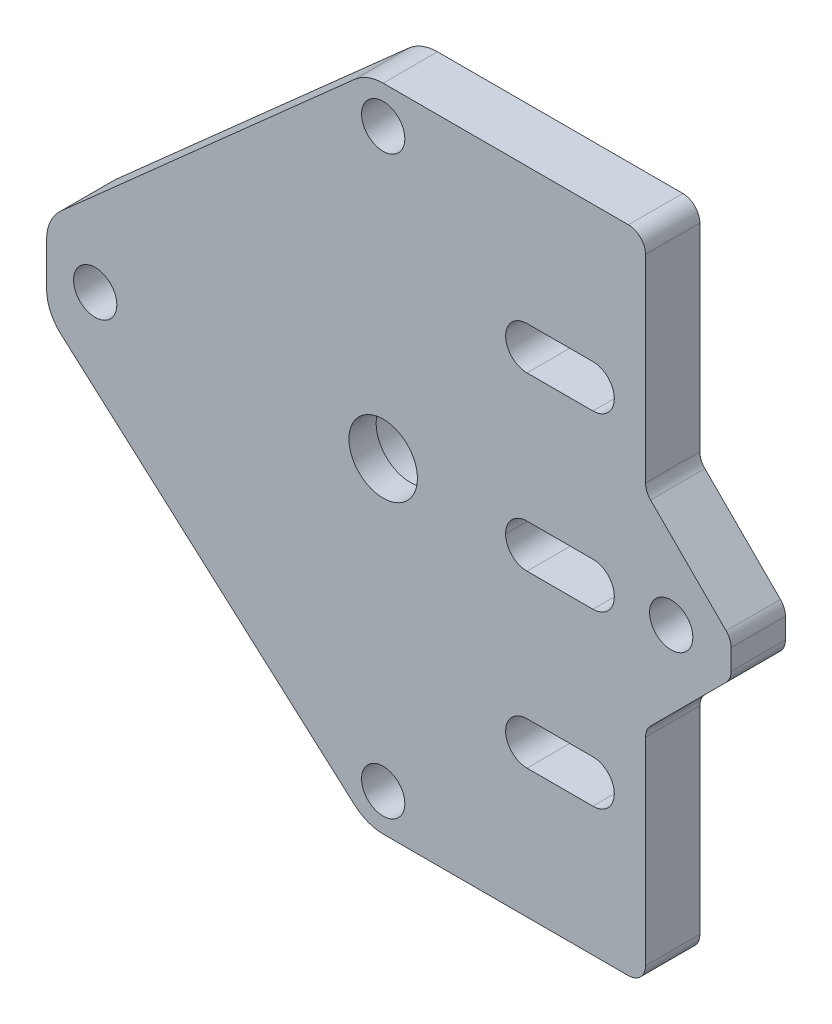
SolidWorks part; units mm, degrees
ref_plane "Front Plane" through (0, 0, 0) normal (0, 0, 1) x (1, 0, 0)
ref_plane "Top Plane" through (0, 0, 0) normal (0, 1, 0) x (1, 0, 0)
ref_plane "Right Plane" through (0, 0, 0) normal (1, 0, 0) x (0, 0, -1)
sketch "Sketch1" plane through (0, 0, 0) normal (0, 0, 1) x (1, 0, 0)
  line L0 (12.9983, -19.5801) -> (-20.66, -19.5801) construction
  line L1 (8, -57.5801) -> (-20.66, -57.5801)
  line L2 (10, -55.5801) -> (10, -32.435)
  line L3 (8, 18.4199) -> (-20.66, 18.4199)
  line L4 (-60, -17.0801) -> (-60, -22.0801)
  line L5 (-20.66, -53.2384) -> (-20.66, 14.0504) construction
  line L6 (-23.9803, 17.1582) -> (-58.3203, -13.3418)
  line L8 (-23.9803, -56.3185) -> (-58.3203, -25.8185)
  line L9 (10, 16.4199) -> (10, -6.7253)
  line L10 (-20.66, 14.0504) -> (-20.66, 18.4199) construction
  line L12 (-20.66, -53.2384) -> (-20.66, -57.5801) construction
  line L14 (-20.66, -19.5801) -> (-54.3183, -19.5801) construction
  line L16 (-54.3183, -19.5801) -> (-60, -19.5801) construction
  line L23 (10.5859, -31.0206) -> (19.4141, -22.1943)
  line L24 (20, -20.7799) -> (20, -18.3803)
  line L25 (19.4141, -16.966) -> (10.5859, -8.1396)
  line L28 (12.9983, -19.5801) -> (20, -19.5801) construction
  circle A0 centre (-20.66, -19.5801) radius 4
  circle A1 centre (-54.3183, -19.5801) radius 2.5277
  circle A2 centre (-20.66, 14.0504) radius 2.5277
  circle A3 centre (12.9983, -19.5801) radius 2.5277
  circle A4 centre (-20.66, -53.2384) radius 2.5277
  arc A5 (10.5859, -8.1396) -> (10, -6.7253) centre (12, -6.7253) cw
  arc A6 (20, -18.3803) -> (19.4141, -16.966) centre (18, -18.3803) ccw
  arc A7 (19.4141, -22.1943) -> (20, -20.7799) centre (18, -20.7799) ccw
  arc A8 (10, -32.435) -> (10.5859, -31.0206) centre (12, -32.435) cw
  arc A9 (-60, -22.0801) -> (-58.3203, -25.8185) centre (-55, -22.0801) ccw
  arc A10 (-23.9803, 17.1582) -> (-20.66, 18.4199) centre (-20.66, 13.4199) cw
  arc A11 (-60, -17.0801) -> (-58.3203, -13.3418) centre (-55, -17.0801) cw
  arc A12 (-23.9803, -56.3185) -> (-20.66, -57.5801) centre (-20.66, -52.5801) ccw
  arc A13 (10, 16.4199) -> (8, 18.4199) centre (8, 16.4199) ccw
  arc A14 (10, -55.5801) -> (8, -57.5801) centre (8, -55.5801) cw
  point P24 (-49.574, 10.4211)
  point P58 (10, -7.5538)
  point P65 (-49.574, -49.5814)
  point P67 (-26.66, 18.5627)
  point P74 (-26.66, -56.4373)
  dimension "D3" = 8
  dimension "D6" = 2
  dimension "D7" = 76
  dimension "D10" = 33.6583
  dimension "D11" = 5.0555
  dimension "D13" = 2
  dimension "D14" = 5
  dimension "D15" = 5
  dimension "D12" = 4.3417
  dimension "D2" = 10
  dimension "D4" = 30.66
  dimension "D5" = 70
  dimension "D8" = 5
  dimension "D9" = 67.2888
  dimension "D16" = 23.1451
extrude "Boss-Extrude1" add sketch "Sketch1" along normal blind 6.35
hole_wizard "Ø5.0mm Dowel Slot1" positions "Sketch3" profile "Sketch2" size "Ø5.0" standard "ANSI Metric" slot yes
sketch "Sketch3" plane through (0, 0, 6.35) normal (0, 0, 1) x (1, 0, 0)
  line L0 (-6.35, -40) -> (6.35, -40) construction
  line L1 (0, -20) -> (0, 0) construction
  line L2 (0, 0) -> (-3.8, 0) construction
  line L4 (0, -20) -> (0, -40) construction
  point P0 (0, -40)
  point P5 (0, -20.0674)
  point P7 (0, 0)
  point P9 (0, -20)
  dimension "D1" = 12.7
sketch "Sketch2" plane through (0, -40, 6.35) normal (1, 0, 0) x (0, -1, 0)
  line L0 (0, 0) -> (0, 11.5022)
  line L1 (0, 11.5022) -> (2.5, 10)
  line L2 (2.5, 10) -> (2.5, 0)
  line L5 (2.5, 0) -> (0, 0)
  line L10 (0, 11.5022) -> (-2.5, 10) construction
  line L11 (0, -6.35) -> (0, 107.95) construction
  dimension "Hole Dia." = 5
  dimension "Hole Depth" = 10
  dimension "Drill Angle" = 118
sketch "Sketch4" plane through (0, 0, 0) normal (0, 0, -1) x (-1, 0, 0)
  circle A0 centre (20.66, -19.5801) radius 4.9268
  circle A1 centre (20.66, -19.5801) radius 4.9268 construction
extrude "Cut-Extrude1" cut sketch "Sketch4" against normal blind 3.175
